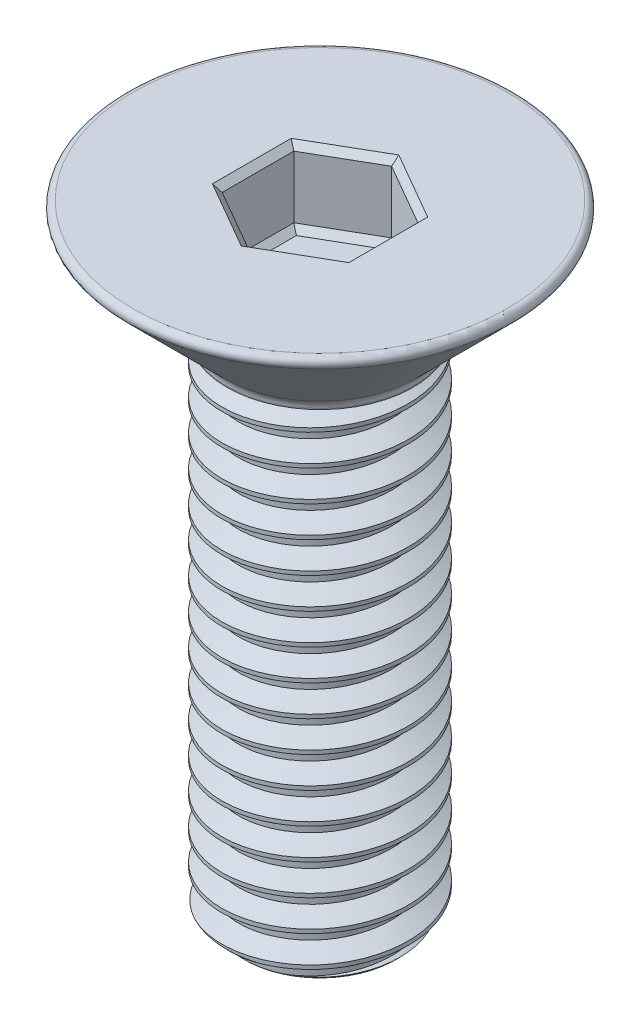
SolidWorks part; units mm, degrees
material "AISI Type A2 Tool Steel"
ref_plane "Front Plane" through (0, 0, 0) normal (0, 0, 1) x (1, 0, 0)
ref_plane "Top Plane" through (0, 0, 0) normal (0, 1, 0) x (1, 0, 0)
ref_plane "Right Plane" through (0, 0, 0) normal (1, 0, 0) x (0, 0, -1)
sketch "Sketch1" plane through (0, 0, 0) normal (0, 1, 0) x (1, 0, 0)
  circle A0 centre (0, 0) radius 1.5
  dimension "D1" = 3
extrude "Boss-Extrude1" add sketch "Sketch1" along normal blind 8.14
thread "Thread1" pitch 0.5 method cut profile "Thread Profile1" start angle 0, offset 1, length 0, pitch 0.5, diameter 3
ref_plane "Plane1" through (-1.5, 9.14, 0) normal (0, 0, 1) x (-1, 0, 0)
sketch "Thread Profile1" plane through (-1.5, 9.14, 0) normal (0, 0, 1) x (-1, 0, 0)
  line L0 (0, 0) -> (0, 0.5) construction
  line L11 (0, 0) -> (0, 0.4375)
  line L12 (0, 0.4375) -> (-0.2706, 0.2812)
  line L13 (-0.2706, 0.2812) -> (-0.2706, 0.1562)
  line L15 (-0.2706, 0.1562) -> (0, 0)
  line L17 (-0.2706, 0.2187) -> (0, 0.2187) construction
  point P2 (0, 0)
  dimension "Pitch" = 0.5
  dimension "Profile_Angle" = 60
  dimension "Profile_Land" = 0.125
  dimension "Profile_Height" = 0.2706
sketch "Sketch5" plane through (0, 8.14, 0) normal (0, 1, 0) x (1, 0, 0)
  circle A0 centre (0, 0) radius 1.5
  dimension "D1" = 3
extrude "Boss-Extrude2" add sketch "Sketch5" along normal blind 0.1
sketch "Sketch6" plane through (0, 8.24, 0) normal (0, 1, 0) x (1, 0, 0)
  circle A0 centre (0, 0) radius 1.5
  dimension "D1" = 3
extrude "Boss-Extrude3" add sketch "Sketch6" along normal blind 1.76 draft 45 draft outward yes
sketch "Sketch7" plane through (0, 0, 0) normal (0, 0, 1) x (1, 0, 0)
  line L0 (0, 0) -> (0, 0.1997) construction
  line L1 (0, 0) -> (1.51, 0) construction
  line L2 (1.51, 0) -> (1.51, 0.3)
  line L3 (1.51, 0.3) -> (1.21, 0)
  line L4 (1.21, 0) -> (1.51, 0)
  dimension "D1" = 45
  dimension "D2" = 0.3
  dimension "D3" = 1.51
revolve "Cut-Revolve1" cut sketch "Sketch7" angle 360 about L0
fillet "Fillet1" radius 0.1 1 edges at (0, 10, 3.26)
fillet "Fillet2" radius 0.2 1 edges at (0, 8.24, 1.5)
sketch "Sketch8" plane through (0, 10, 0) normal (0, 1, 0) x (1, 0, 0)
  line L1 (0, 1.1547) -> (-1, 0.5774)
  line L2 (-1, 0.5774) -> (-1, -0.5774)
  line L3 (-1, -0.5774) -> (0, -1.1547)
  line L4 (0, -1.1547) -> (1, -0.5774)
  line L5 (1, -0.5774) -> (1, 0.5774)
  line L6 (1, 0.5774) -> (0, 1.1547)
  circle A0 centre (0, 0) radius 1 construction
  dimension "D1" = 2
extrude "Cut-Extrude1" cut sketch "Sketch8" against normal blind 1.1
chamfer "Chamfer1" distance 0.1 angle 45 6 edges at (-1, 10, 0) (-0.5, 10, 0.866) (0.5, 10, 0.866) (1, 10, 0) (0.5, 10, -0.866) (-0.5, 10, -0.866)
sketch "Sketch9" plane through (0, 8.9, 0) normal (0, 1, 0) x (1, 0, 0)
  line L1 (0, 1.1547) -> (-1, 0.5774)
  line L2 (-1, 0.5774) -> (-1, -0.5774)
  line L3 (-1, -0.5774) -> (0, -1.1547)
  line L4 (0, -1.1547) -> (1, -0.5774)
  line L5 (1, -0.5774) -> (1, 0.5774)
  line L6 (1, 0.5774) -> (0, 1.1547)
  circle A0 centre (0, 0) radius 1 construction
extrude "Cut-Extrude2" cut sketch "Sketch9" against normal blind 0.1 draft 45
